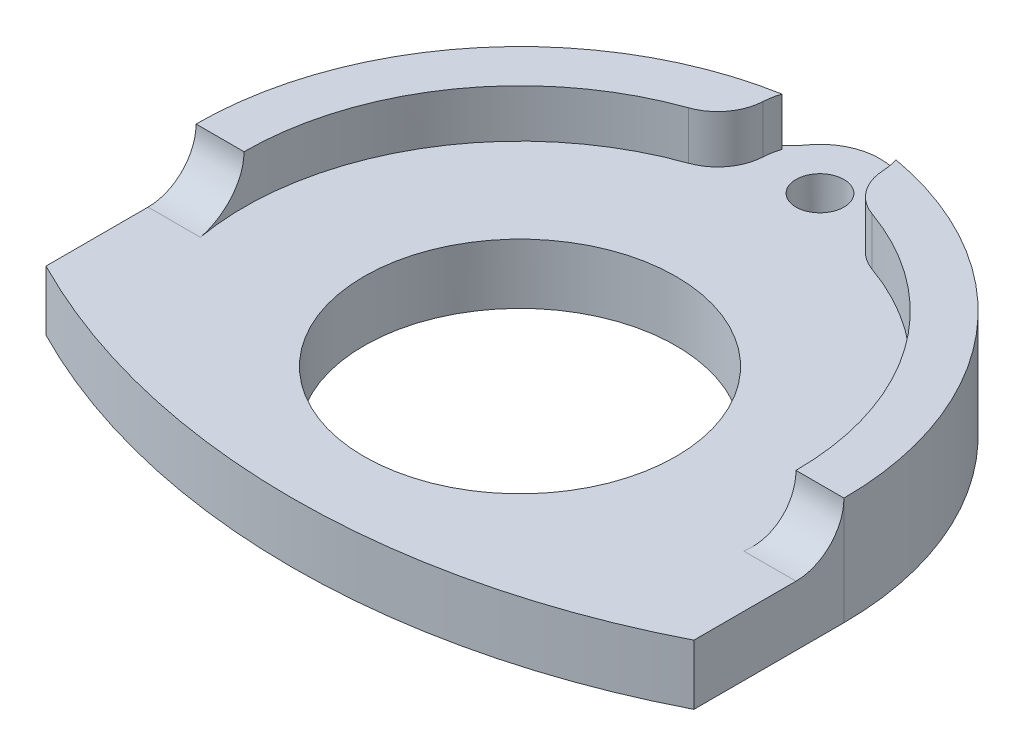
SolidWorks part; units mm, degrees
ref_plane "Front Plane" through (0, 0, 0) normal (0, 0, 1) x (1, 0, 0)
ref_plane "Top Plane" through (0, 0, 0) normal (0, 1, 0) x (1, 0, 0)
ref_plane "Right Plane" through (0, 0, 0) normal (1, 0, 0) x (0, 0, -1)
sketch "Sketch1" plane through (0, 2.5, 0) normal (0, -1, 0) x (1, 0, 0)
  line L0 (-13.5, 26.4376) -> (-13.5, 20.185)
  line L1 (13.5, 26.4376) -> (13.5, 20.185)
  circle A11 centre (0, 20.185) radius 6.5
  circle A12 centre (0, 20.185) radius 9.5 construction
  arc A13 (-13.5, 20.185) -> (-2.3719, 6.895) centre (0, 20.185) ccw
  arc A14 (-11.3495, 22.0397) -> (-3.8283, 9.3409) centre (0, 20.185) ccw construction
  circle A23 centre (0, 0) radius 29.685 construction
  arc A24 (13.5, 26.4376) -> (-13.5, 26.4376) centre (0, 0) ccw
  arc A25 (-2.4967, 7.5572) -> (2.4967, 7.5572) centre (0, 7.685) ccw construction
  arc A26 (-2.3719, 6.895) -> (2.3719, 6.895) centre (0, 7.685) ccw
  arc A27 (2.3719, 6.895) -> (13.5, 20.185) centre (0, 20.185) ccw
  circle A28 centre (0, 7.685) radius 1 construction
  circle A29 centre (0, 7.685) radius 1
  dimension "D1" = 3
  dimension "D2" = 2
extrude "Main extrude" add sketch "Sketch1" along normal up to surface (2.5 mm away)
sketch "Sketch2" plane through (0, 2.5, 0) normal (0, 1, 0) x (1, 0, 0)
  line L3 (-13.5, -20.185) -> (-11.5, -20.185)
  line L4 (13.5, -20.185) -> (11.5, -20.185)
  arc A15 (-3.8283, -9.3409) -> (-11.3495, -22.0397) centre (0, -20.185) ccw construction
  arc A16 (-2.3719, -6.895) -> (-13.5, -20.185) centre (0, -20.185) ccw construction
  arc A17 (-3.8283, -9.3409) -> (-2.4967, -7.5572) centre (-4.4941, -7.455) ccw construction
  arc A18 (11.3495, -22.0397) -> (3.8283, -9.3409) centre (0, -20.185) ccw construction
  arc A19 (2.4967, -7.5572) -> (3.8283, -9.3409) centre (4.4941, -7.455) ccw construction
  arc A20 (2.4967, -7.5572) -> (-2.4967, -7.5572) centre (0, -7.685) ccw construction
  arc A21 (13.5, -20.185) -> (2.3719, -6.895) centre (0, -20.185) ccw construction
  arc A22 (-3.8283, -9.3409) -> (-11.5, -20.185) centre (0, -20.185) ccw
  arc A23 (-2.3719, -6.895) -> (-13.5, -20.185) centre (0, -20.185) ccw
  arc A24 (-3.8283, -9.3409) -> (-2.4967, -7.5572) centre (-4.4941, -7.455) ccw
  arc A25 (11.5, -20.185) -> (3.8283, -9.3409) centre (0, -20.185) ccw
  arc A26 (2.4967, -7.5572) -> (3.8283, -9.3409) centre (4.4941, -7.455) ccw
  arc A27 (2.4967, -7.5572) -> (2.3719, -6.895) centre (0, -7.685) ccw
  arc A28 (13.5, -20.185) -> (2.3719, -6.895) centre (0, -20.185) ccw
  arc A29 (-2.3719, -6.895) -> (-2.4967, -7.5572) centre (0, -7.685) ccw
extrude "Battery ring craddle" add sketch "Sketch2" along normal blind 2
fillet "Fillets" radius 2 4 edges at (2.3719, 1.25, 6.895) (-2.3719, 1.25, 6.895) (-12.5, 2.5, 20.185) (12.5, 2.5, 20.185)
